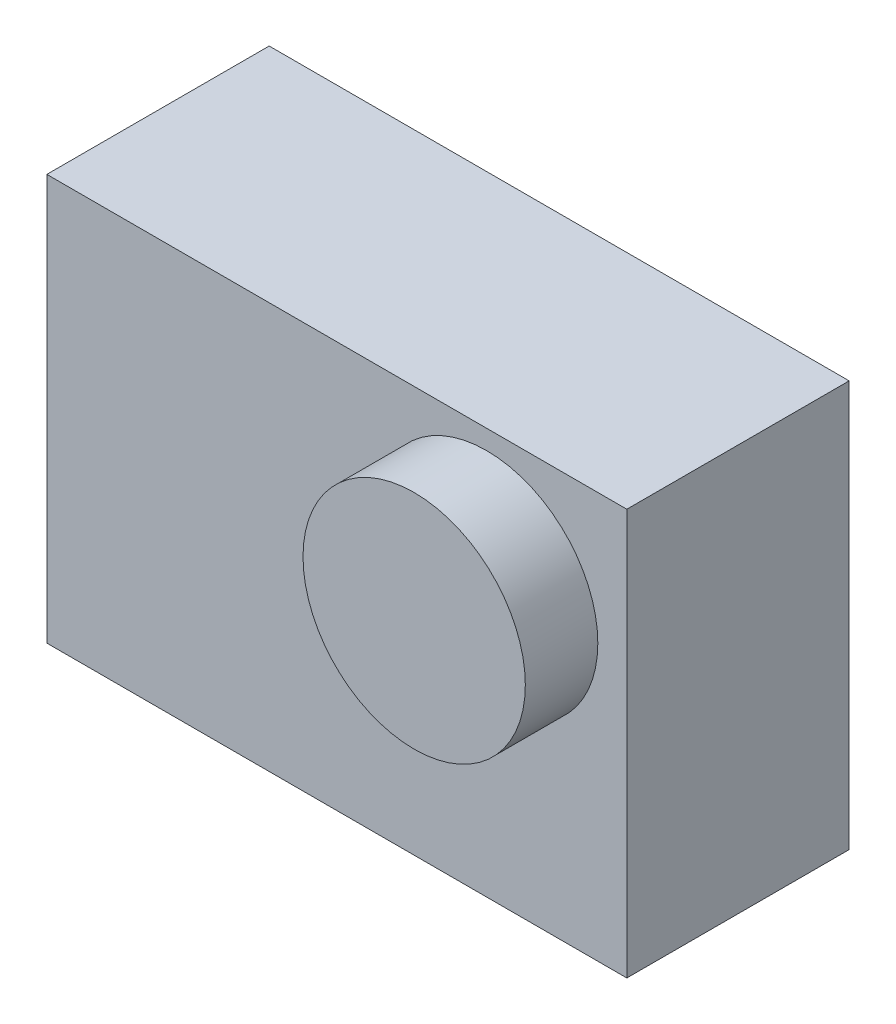
SolidWorks part; units mm, degrees
ref_plane "Front Plane" through (0, 0, 0) normal (0, 0, 1) x (1, 0, 0)
ref_plane "Top Plane" through (0, 0, 0) normal (0, 1, 0) x (1, 0, 0)
ref_plane "Right Plane" through (0, 0, 0) normal (1, 0, 0) x (0, 0, -1)
sketch "Эскиз1" plane through (0, 0, 0) normal (0, 0, 1) x (1, 0, 0)
  line L1 (-30, -21) -> (30, -21)
  line L2 (-30, -21) -> (-30, 21)
  line L3 (-30, 21) -> (30, 21)
  line L4 (30, -21) -> (30, 21)
  line L5 (-30, -21) -> (30, 21) construction
  line L6 (-30, 21) -> (30, -21) construction
  circle A0 centre (15.5, 7.5) radius 11.5
  point P0 (0, 0)
  point P8 (-108.2515, 8.5273)
  point P11 (30, 14.1273)
  dimension "D3" = 23
  dimension "D4" = 2
  dimension "D5" = 3
  dimension "D1" = 42
  dimension "D2" = 60
extrude "Бобышка-Вытянуть1" add sketch "Эскиз1" along normal mid plane 23 contours A0 | L1 L4 L3 L2 A0 region at (-3.06, -1.4807, 0) region at (15.5, 7.5, 0)
extrude "Бобышка-Вытянуть2" add sketch "Эскиз1<3>" along normal blind 7.5 from surface contours A0 region at (15.5, 7.5, 0) starting at face at (0, 0, 11.5)
sketch "Эскиз1<3>" plane through (0, 0, 0) normal (0, 0, 1) x (1, 0, 0) same geometry as "Эскиз1"
